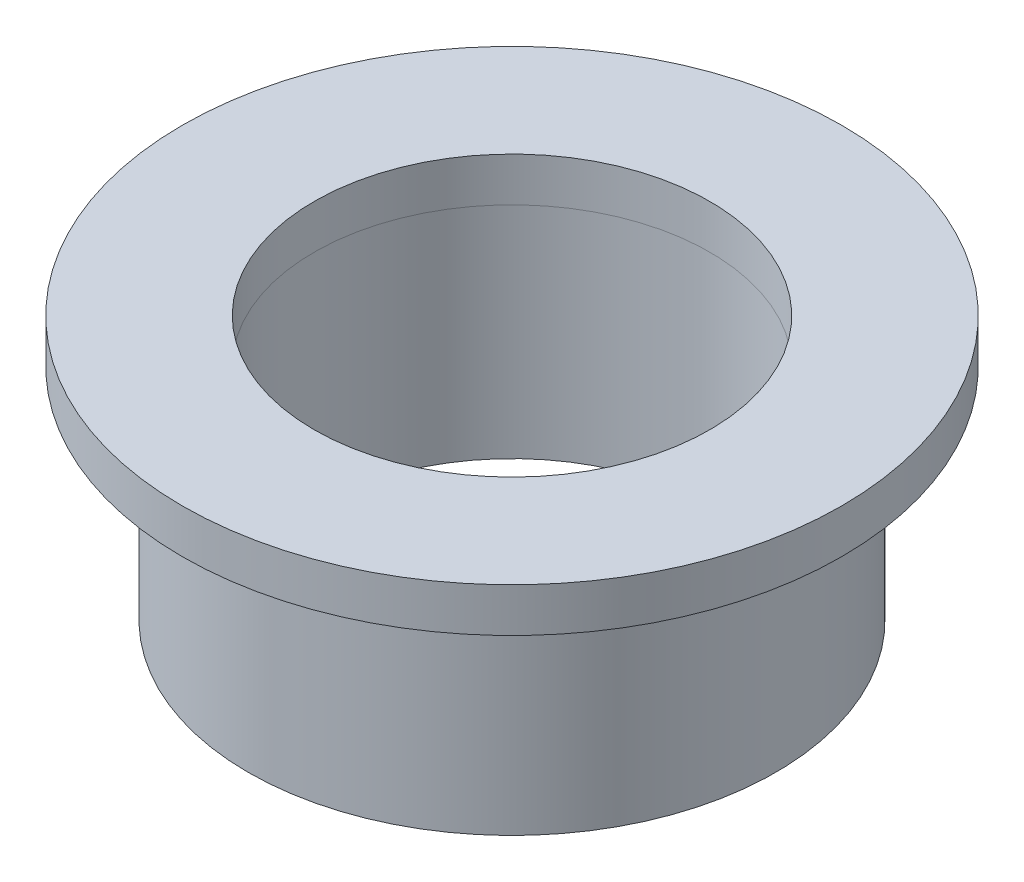
SolidWorks part; units mm, degrees
ref_plane "Front Plane" through (0, 0, 0) normal (0, 0, 1) x (1, 0, 0)
ref_plane "Top Plane" through (0, 0, 0) normal (0, 1, 0) x (1, 0, 0)
ref_plane "Right Plane" through (0, 0, 0) normal (1, 0, 0) x (0, 0, -1)
sketch "Sketch1" plane through (0, 0, 0) normal (0, 1, 0) x (1, 0, 0)
  circle A0 centre (0, 0) radius 6
  circle A1 centre (0, 0) radius 4.5
  circle A2 centre (0, 0) radius 7.5
  dimension "D1" = 12
  dimension "D2" = 9
  dimension "D3" = 15
extrude "Boss-Extrude1" add sketch "Sketch1" along normal blind 1 contours A0 A1 | A2 A0 region at (-5.8303, 0, 0) region at (-7.2879, 0, 0)
extrude "Boss-Extrude2" add sketch "Sketch1<3>" against normal blind 5 separate body contours A0 | A1
sketch "Sketch1<3>" plane through (0, 0, 0) normal (0, 1, 0) x (1, 0, 0) same geometry as "Sketch1"
